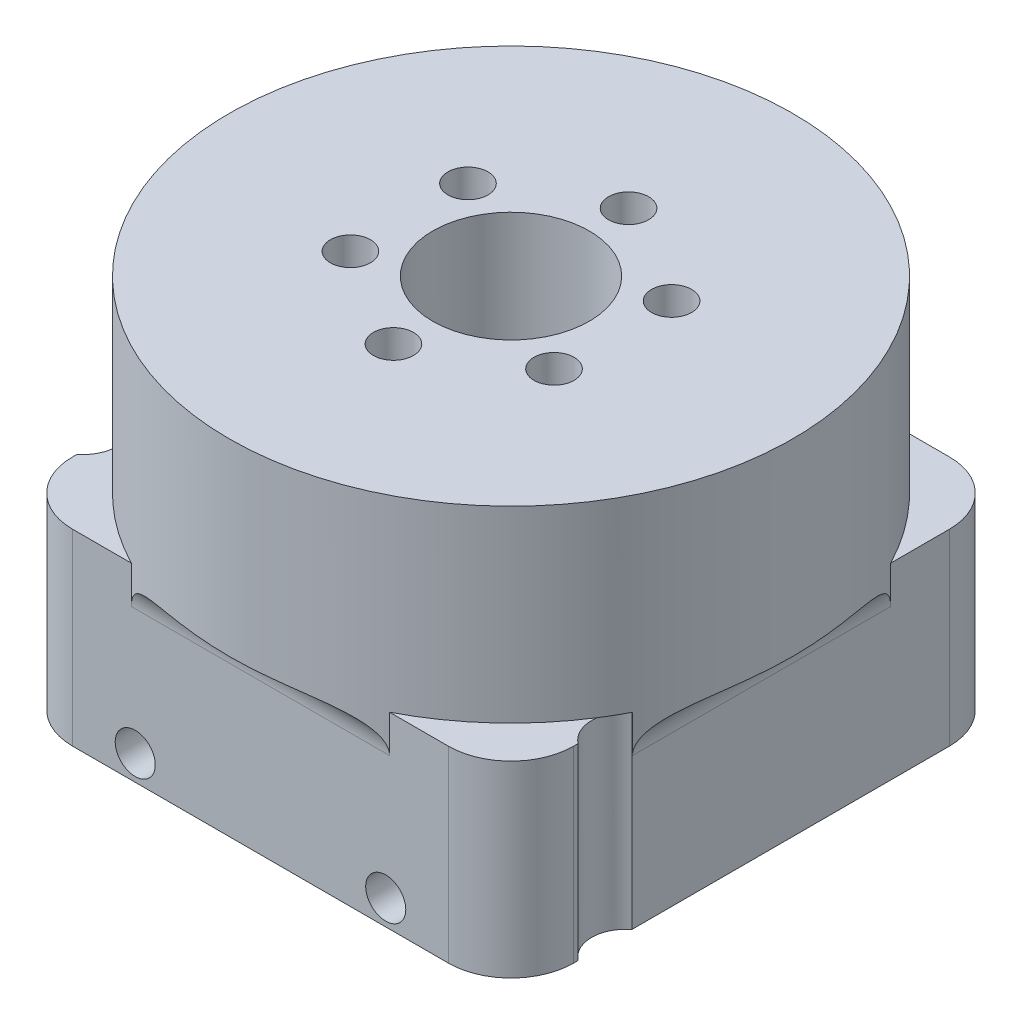
SolidWorks part; units mm, degrees
ref_plane "Front Plane" through (0, 0, 0) normal (0, 0, 1) x (1, 0, 0)
ref_plane "Top Plane" through (0, 0, 0) normal (0, 1, 0) x (1, 0, 0)
ref_plane "Right Plane" through (0, 0, 0) normal (1, 0, 0) x (0, 0, -1)
sketch "Sketch1" plane through (0, 0, 0) normal (0, 1, 0) x (1, 0, 0)
  line L0 (0, 0) -> (0, 35.4208) construction
  line L1 (-20, -20) -> (20, -20)
  line L2 (-20, -20) -> (-20, 20)
  line L3 (-20, 20) -> (20, 20)
  line L4 (20, -20) -> (20, 20)
  line L5 (-20, -20) -> (20, 20) construction
  line L6 (-20, 20) -> (20, -20) construction
  circle A0 centre (0, 0) radius 6.25
  circle A1 centre (0, 25) radius 2.7073
  circle A2 centre (21.6506, -12.5) radius 2.7073
  circle A3 centre (-21.6506, -12.5) radius 2.7073
  point P0 (0, 0)
  point P18 (0, 0)
  dimension "D2" = 12.5
  dimension "D1" = 25
  dimension "D3" = 40
  dimension "D4" = 40
  dimension "D5" = 3
extrude "Boss-Extrude1" add sketch "Sketch1" along normal blind 15 contours A3 L2 L1 L4 A2 L3 A0 region at (-19.4343, 0, 17.3229)
sketch "Sketch7" plane through (0, 15, 0) normal (0, 1, 0) x (1, 0, 0)
  circle A0 centre (0, 0) radius 22.5
  circle A1 centre (0, 0) radius 6.25
  dimension "D1" = 45
  dimension "D2" = 12.5
extrude "Boss-Extrude2" add sketch "Sketch7" along normal blind 15
sketch "Sketch5" plane through (0, 0, 0) normal (1, 0, 0) x (0, 0, -1)
  line L0 (-10.331, 15) -> (10.331, 0) construction
  line L1 (10, 5) -> (-10, 5)
  line L2 (10, 5) -> (10, 10)
  line L3 (10, 10) -> (-10, 10)
  line L4 (-10, 5) -> (-10, 10)
  line L5 (10, 5) -> (-10, 10) construction
  line L6 (10, 10) -> (-10, 5) construction
  line L7 (20, 7.5) -> (-20, 7.5) construction
  line L8 (20, 15) -> (20, 0) construction
  line L9 (-20, 15) -> (-20, 0) construction
  line L10 (-10.3541, 15) -> (-10.3078, 15) construction
  line L11 (-10.3541, 0) -> (20, 0) construction
  point P0 (0, 7.5)
  dimension "D1" = 20
  dimension "D2" = 5
extrude "Square side-insert" [suppressed] cut sketch "Sketch5" against normal up to surface (20 mm away) up to face at (-20, 10, -3.2153)
sketch "Sketch3" plane through (0, 0, -20) normal (0, 0, -1) x (-1, 0, 0)
  line L3 (15.1539, 15) -> (15.1539, 3) construction
  line L4 (20, 15) -> (10.3078, 15) construction
  circle A0 centre (15.1539, 3) radius 1.6
  dimension "D2" = 3.2
  dimension "D1" = 12
extrude "Single Screw" cut sketch "Sketch3" against normal blind 17
sketch "Sketch2" plane through (0, 0, 20) normal (0, 0, 1) x (1, 0, 0)
  line L0 (0, 27.8717) -> (0, -11.9207) construction
  line L1 (20, 2) -> (10, 2)
  line L3 (10, 2) -> (10, 0)
  line L4 (-20, 0) -> (20, 0) construction
  line L5 (20, 15) -> (20, 0) construction
  circle A0 centre (10, 2) radius 1.6
  circle A1 centre (-10, 2) radius 1.6
  dimension "D3" = 3.2
  dimension "D1" = 10
  dimension "D2" = 2
extrude "Double Screw" cut sketch "Sketch2" against normal blind 10 contours A1 | A0
sketch "Sketch6" plane through (0, 30, 0) normal (0, 1, 0) x (1, 0, 0)
  circle A9 centre (0, -9.385) radius 1.6
  circle A10 centre (-8.1276, -4.6925) radius 1.6
  circle A11 centre (-8.1276, 4.6925) radius 1.6
  circle A12 centre (0, 9.385) radius 1.6
  circle A13 centre (8.1276, 4.6925) radius 1.6
  circle A14 centre (8.1276, -4.6925) radius 1.6
  point P16 (0, 0)
  dimension "D2" = 9.385
  dimension "D1" = 3.2
  dimension "D3" = 9.385
extrude "Cut-Extrude1" cut sketch "Sketch6" against normal through all
sketch "Sketch8" plane through (0, 15, 0) normal (0, 1, 0) x (1, 0, 0)
  line L0 (-20, 5) -> (-20, -5)
  line L1 (-20, -5) -> (-3.75, -5) construction
  line L2 (-20, 5) -> (-3.75, 5) construction
  line L3 (-20, -10.3541) -> (-20, -10.3078) construction
  line L4 (-20, 5) -> (-20, 12.5)
  line L6 (-20, -5) -> (-20, -12.5)
  line L8 (-20, 12.5) -> (-13.9645, 6.4645)
  line L9 (-10.4289, 5) -> (-3.75, 5)
  line L10 (-20, -12.5) -> (-13.9645, -6.4645)
  line L11 (-10.4289, -5) -> (-3.75, -5)
  circle A0 centre (0, 0) radius 6.25 construction
  arc A1 (-3.75, 5) -> (-3.75, -5) centre (0, 0) ccw
  arc A2 (-13.9645, -6.4645) -> (-10.4289, -5) centre (-10.4289, -10) cw
  arc A3 (-10.4289, 5) -> (-13.9645, 6.4645) centre (-10.4289, 10) cw
  point P6 (-20, 0)
  point P19 (-12.5, -5)
  point P22 (-12.5, 5)
  dimension "D2" = 7.5
  dimension "D5" = 5
  dimension "D1" = 10
  dimension "D3" = 7.5
  dimension "D4" = 7.5
extrude "Cut-Extrude3" cut sketch "Sketch8" against normal blind 5 from offset 5 offset against normal yes
fillet "Fillet2" radius 5 4 edges at (20, 7.5, 20) (20, 7.5, -20) (-20, 7.5, -20) (-20, 7.5, 20)
fillet "Fillet3" radius 3 4 edges at (-20, 15, 0) (0, 15, -20) (20, 15, 0) (0, 15, 20)
